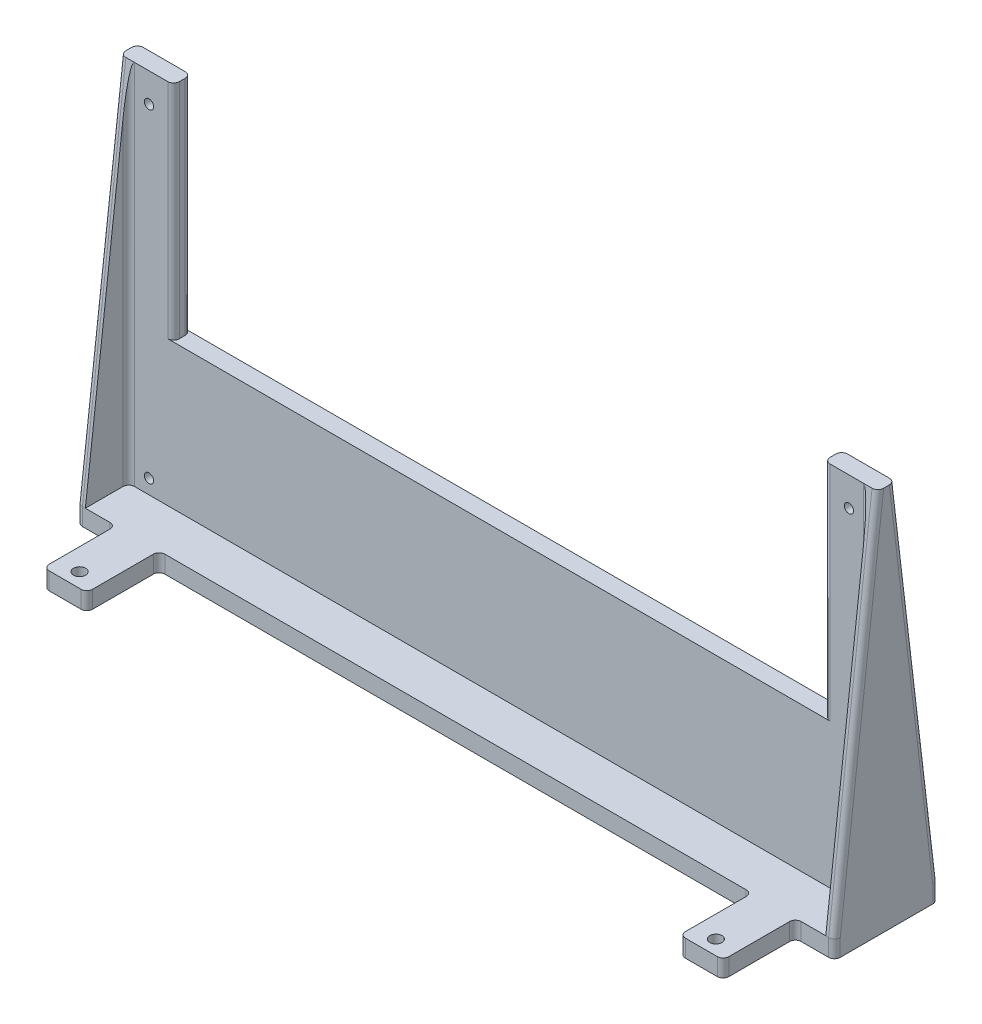
SolidWorks part; units mm, degrees
ref_plane "Front Plane" through (0, 0, 0) normal (0, 0, 1) x (1, 0, 0)
ref_plane "Top Plane" through (0, 0, 0) normal (0, 1, 0) x (1, 0, 0)
ref_plane "Right Plane" through (0, 0, 0) normal (1, 0, 0) x (0, 0, -1)
sketch "Sketch1" plane through (0, 0, 0) normal (0, 0, 1) x (1, 0, 0)
  line L1 (-121, -56) -> (121, -56) construction
  line L2 (-121, -56) -> (-121, 56) construction
  line L3 (-121, 56) -> (121, 56) construction
  line L4 (121, -56) -> (121, 56) construction
  line L5 (-121, -56) -> (121, 56) construction
  line L6 (-121, 56) -> (121, -56) construction
  line L7 (-131, -66) -> (131, -66) construction
  line L8 (-131, -66) -> (-131, 66)
  line L9 (-131, 66) -> (131, 66)
  line L10 (131, -66) -> (131, 66)
  line L11 (-131, -66) -> (131, 66) construction
  line L12 (-131, 66) -> (131, -66) construction
  line L13 (-131, -66) -> (131, -66) construction
  line L14 (-131, -66) -> (-131, -67)
  line L15 (-131, -67) -> (131, -67)
  line L16 (131, -66) -> (131, -67)
  circle A0 centre (-121, 56) radius 1.6
  circle A1 centre (121, 56) radius 1.6
  circle A2 centre (121, -56) radius 1.6
  circle A3 centre (-121, -56) radius 1.6
  point P0 (0, 0)
  point P6 (0, 0)
  dimension "D1" = 3.2
  dimension "D2" = 242
  dimension "D3" = 112
  dimension "D4" = 10
  dimension "D5" = 10
  dimension "D6" = 1
extrude "Boss-Extrude1" add sketch "Sketch1" along normal blind 6
sketch "Sketch5" plane through (0, 0, 6) normal (0, 0, 1) x (1, 0, 0)
  line L0 (131, -67) -> (131, 66) construction
  line L1 (-131, -67) -> (131, -67)
  line L2 (-131, -67) -> (-131, -61)
  line L3 (-131, -61) -> (131, -61)
  line L4 (131, -67) -> (131, -61)
  dimension "D1" = 6
extrude "Boss-Extrude3" add sketch "Sketch5" along normal blind 40
extrude "Boss-Extrude5" add sketch "Sketch5<2>" against normal blind 30
sketch "Sketch5<2>" plane through (0, 0, 6) normal (0, 0, 1) x (1, 0, 0) same geometry as "Sketch5"
sketch "Sketch3" plane through (0, -61, 0) normal (0, 1, 0) x (1, 0, 0)
  line L0 (-131, -41) -> (131, -41) construction
  line L1 (-131, 19) -> (131, 19) construction
  line L2 (-131, 24) -> (-131, 0) construction
  line L3 (131, 24) -> (131, 0) construction
  line L4 (131, 24) -> (-131, 24) construction
  line L5 (131, -46) -> (-131, -46) construction
  line L6 (-131, -46) -> (-131, -6) construction
  line L7 (131, -46) -> (131, -6) construction
  line L8 (-110, -41) -> (110, -41) construction
  line L9 (-90, 19) -> (0, 0) construction
  line L10 (-110, -41) -> (110, -41) construction
  line L11 (0, 0) -> (90, 19) construction
  line L12 (-90, 19) -> (90, 19) construction
  circle A0 centre (-110, -41) radius 2.1
  circle A1 centre (110, -41) radius 2.1
  circle A2 centre (-90, 19) radius 2.1
  circle A3 centre (90, 19) radius 2.1
  point P22 (0, -41)
  dimension "D1" = 4.2
  dimension "D2" = 220
  dimension "D3" = 5
  dimension "D4" = 5
  dimension "D5" = 180
extrude "Cut-Extrude1" cut sketch "Sketch3" against normal through all
sketch "Sketch6" plane through (0, 0, 6) normal (0, 0, 1) x (1, 0, 0)
  line L0 (0, 66) -> (0, -67) construction
  line L1 (131, 66) -> (-131, 66) construction
  line L2 (-131, -67) -> (131, -67) construction
  line L3 (131, -61) -> (-131, -61) construction
  line L4 (-112.5, -11) -> (112.5, -11)
  line L5 (-112.5, -11) -> (-112.5, 66)
  line L6 (-112.5, 66) -> (112.5, 66)
  line L7 (112.5, -11) -> (112.5, 66)
  line L8 (-112.5, -11) -> (112.5, 66) construction
  line L9 (-112.5, 66) -> (112.5, -11) construction
  point P6 (0, 27.5)
  point P18 (121, 56)
  dimension "D1" = 225
  dimension "D2" = 50
extrude "Cut-Extrude2" cut sketch "Sketch6" against normal through all
sketch "Sketch9" plane through (0, -61, 0) normal (0, 1, 0) x (1, 0, 0)
  line L0 (-81.5, 24) -> (-81.5, 0)
  line L1 (131, 24) -> (-131, 24) construction
  line L2 (-131, 0) -> (131, 0) construction
  line L3 (-81.5, 0) -> (-77.5, 0)
  line L4 (-77.5, 0) -> (-77.5, 20)
  line L5 (-77.5, 20) -> (77.5, 20) construction
  line L6 (77.5, 20) -> (77.5, 0)
  line L7 (81.5, 24) -> (-81.5, 24) construction
  line L8 (77.5, 0) -> (81.5, 0)
  line L9 (112.5, 0) -> (-112.5, 0) construction
  line L10 (81.5, 0) -> (81.5, 24)
  line L11 (0, 20) -> (0, 24) construction
  line L12 (81.5, 24) -> (57.5, 24)
  line L13 (57.5, 24) -> (57.5, 20)
  line L14 (57.5, 20) -> (77.5, 20)
  line L15 (-81.5, 24) -> (-57.5, 24)
  line L16 (-57.5, 24) -> (-57.5, 20)
  line L17 (-57.5, 20) -> (-77.5, 20)
  line L18 (0, 20) -> (0, 0) construction
  dimension "D1" = 155
  dimension "D3" = 4
extrude "Boss-Extrude7" add sketch "Sketch9" along normal blind 20
sketch "Sketch11" plane through (0, -61, 0) normal (0, 1, 0) x (1, 0, 0)
  line L0 (-131, 24) -> (-95, 24)
  line L1 (-131, 24) -> (-131, 15)
  line L2 (-131, 15) -> (-95, 15)
  line L3 (-95, 24) -> (-95, 15)
  line L4 (131, 24) -> (95, 24)
  line L5 (131, 24) -> (131, 15)
  line L6 (131, 15) -> (95, 15)
  line L7 (95, 24) -> (95, 15)
  line L8 (131, -46) -> (117.5, -46)
  line L9 (131, -46) -> (131, -21)
  line L10 (131, -21) -> (117.5, -21)
  line L11 (117.5, -46) -> (117.5, -21)
  line L12 (-131, -46) -> (-117.5, -46)
  line L13 (-131, -46) -> (-131, -21)
  line L14 (-131, -21) -> (-117.5, -21)
  line L15 (-117.5, -46) -> (-117.5, -21)
  line L16 (-102.5, -46) -> (102.5, -46)
  line L17 (-102.5, -46) -> (-102.5, -21)
  line L18 (-102.5, -21) -> (102.5, -21)
  line L19 (102.5, -46) -> (102.5, -21)
  line L20 (0, -21) -> (0, 0) construction
  line L21 (-112.5, -3) -> (-112.5, 15) construction
  line L22 (-112.5, -3) -> (-112.5, -21) construction
  line L23 (-117.5, -41) -> (-102.5, -41) construction
  line L24 (102.5, -41) -> (117.5, -41) construction
  line L25 (131, -46) -> (-131, -46) construction
  line L26 (-112.5, -6) -> (-112.5, 0) construction
  circle A0 centre (-90, 19) radius 2.1 construction
  point P27 (-110, -41)
  point P30 (110, -41)
  point P31 (131, 24)
  point P33 (131, -46)
  point P35 (-5.4037, -46)
  point P36 (0, -39.1835)
  point P37 (0, 0)
  point P38 (100, -41)
  point P40 (115.2721, -33.982)
  point P41 (-29.5909, -31.1211)
  point P42 (-100, -41)
  point P44 (-107.5, -46)
  point P47 (-131, -46)
  point P49 (-131, 24)
  point P51 (-119.3175, 5.2897)
  point P52 (0, 0)
  point P54 (-112.5, -3)
  point P57 (-92.5, -46)
  dimension "D1" = 18
  dimension "D2" = 15
  dimension "D3" = 5
extrude "Cut-Extrude4" cut sketch "Sketch11" against normal through all both and the other way through all
sketch "Sketch8" plane through (131, 0, 0) normal (1, 0, 0) x (0, 0, -1)
  line L0 (-6, 66) -> (-21, -61)
  line L1 (-6, 66) -> (-6, -61)
  line L2 (-6, -61) -> (-21, -61)
  line L3 (0, 66) -> (0, -61)
  line L4 (0, -61) -> (15, -61)
  line L5 (15, -61) -> (0, 66)
  line L7 (15, -61) -> (0, -61) construction
  line L8 (-21, -67) -> (-21, -61) construction
  line L9 (-21, -67) -> (-21, -61) construction
  point P10 (0, 0)
  point P13 (24, -61)
  point P14 (15, -61)
  point P18 (0, 0)
  point P19 (0, 0)
  point P20 (0, 0)
  point P21 (-21, -61)
  point P26 (0, 0)
  point P27 (24, -61)
extrude "Boss-Extrude4" add sketch "Sketch8" against normal blind 3
sketch "Sketch7" plane through (-131, 0, 0) normal (-1, 0, 0) x (0, 0, 1)
  line L0 (6, 66) -> (21, -61)
  line L1 (6, 66) -> (6, -61)
  line L2 (6, -61) -> (21, -61)
  line L3 (0, 66) -> (-15, -61)
  line L4 (-15, -61) -> (0, -61)
  line L5 (0, -61) -> (0, 66)
  line L6 (0, 66) -> (0, -61) construction
  point P10 (0, 0)
  point P13 (0, 0)
  point P14 (0, -61)
  point P17 (-24, -61)
  point P19 (0, 0)
  point P20 (0, 0)
  point P21 (21, -61)
  point P23 (0, 0)
  point P24 (-14.7259, -59.8897)
  point P25 (-15, -61)
extrude "Boss-Extrude6" add sketch "Sketch7" against normal blind 3
fillet "Fillet1" radius 2 40 edges at (128, 2.5, 6) (128, 2.5, 0) (-128, 2.5, 0) (-131, 2.5, -7.5) (-131, 2.5, 13.5) (-128, 2.5, 6) (131, 2.5, -7.5) (131, 2.5, 13.5) (-112.5, 27.5, 6) (-112.5, 27.5, 0) (112.5, 27.5, 6) (112.5, 27.5, 0) (-131, -64, -15) (-95, -64, -15) (-95, -64, -24) (-81.5, -51, 0) (81.5, -51, 0) (95, -64, -24) (95, -64, -15) (131, -64, -15) (-131, -64, 21) (-117.5, -64, 21) (102.5, -64, 21) (131, -64, 21) (-102.5, -64, 21) (117.5, -64, 21) (102.5, -64, 46) (117.5, -64, 46) (-117.5, -64, 46) (-102.5, -64, 46) (77.5, -51, 0) (-77.5, -51, 0) (-77.5, -51, -20) (77.5, -51, -20) (57.5, -51, -20) (-57.5, -51, -20) (-81.5, -51, -24) (-57.5, -51, -24) (57.5, -51, -24) (81.5, -51, -24)
